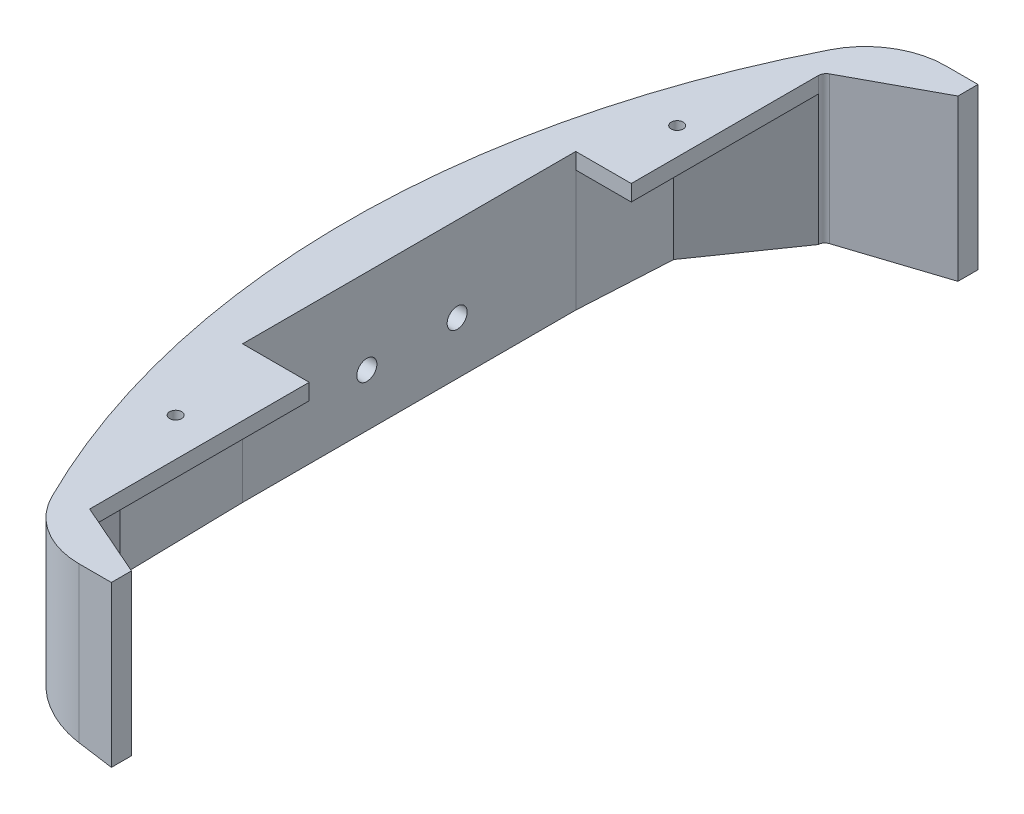
SolidWorks part; units mm, degrees
ref_plane "Front Plane" through (0, 0, 0) normal (0, 0, 1) x (1, 0, 0)
ref_plane "Top Plane" through (0, 0, 0) normal (0, 1, 0) x (1, 0, 0)
ref_plane "Right Plane" through (0, 0, 0) normal (1, 0, 0) x (0, 0, -1)
sketch "front_sketch" plane through (0, 0, 0) normal (0, 1, 0) x (1, 0, 0)
  line L4 (-94.9614, 124.4785) -> (-121.3453, 110.2345)
  line L10 (-122.6787, 107.9994) -> (-122.6787, 48.8108)
  line L24 (-94.9614, 130.8285) -> (-94.9614, 124.4785) construction
  line L25 (-94.9614, 124.4785) -> (-69.5614, 124.4785) construction
  line L28 (-95.6016, -142.8102) -> (-95.6016, -136.4602)
  line L29 (-95.6016, -136.4602) -> (-70.2016, -136.4602) construction
  line L34 (-122.6787, 48.8108) -> (-140.2508, 48.8108)
  line L36 (-140.2508, 48.8108) -> (-140.2508, -56.6452)
  line L43 (-140.2508, -56.6452) -> (-119.167, -56.6452)
  line L44 (-119.167, -56.6452) -> (-119.167, -126.1123)
  line L50 (-119.167, -126.1123) -> (-95.6016, -136.4602)
  line L129 (-94.9614, 130.8285) -> (-69.5614, 130.8285) construction
  line L130 (-94.9614, 130.8285) -> (-69.5614, 130.8285) construction
  line L225 (-95.5505, 130.8285) -> (-157.7358, 130.8285) construction
  line L248 (-94.9614, 130.8285) -> (-95.5505, 130.8285) construction
  line L254 (-94.9614, 130.8285) -> (-95.5505, 130.8285) construction
  line L257 (-94.9614, 130.8285) -> (-105.2412, 130.8285)
  line L258 (-95.5505, 130.8285) -> (-94.9614, 130.8285) construction
  line L259 (-95.6016, -142.8102) -> (-105.7982, -142.8102)
  line L260 (-94.9614, 124.4785) -> (-94.9614, 130.8285)
  line L261 (-94.9614, 130.8285) -> (-95.5505, 130.8285) construction
  line L263 (-95.6016, -142.8102) -> (-70.2016, -142.8102) construction
  line L264 (-95.6016, -142.8102) -> (-70.2016, -142.8102) construction
  line L267 (-97.1554, -142.8102) -> (-95.6016, -142.8102) construction
  line L294 (-94.9614, 130.8285) -> (-95.5505, 130.8285) construction
  line L295 (-157.7358, 130.8285) -> (-157.7358, -142.8102) construction
  line L296 (-157.7358, -142.8102) -> (-97.1554, -142.8102) construction
  line L297 (-95.5505, 130.8285) -> (-157.7358, 130.8285) construction
  arc A41 (-127.9188, 116.8691) -> (-128.5327, -128.7374) centre (116.7138, -6.5464) ccw
  arc A42 (-127.9188, 116.8691) -> (-105.2412, 130.8285) centre (-105.2412, 105.4285) cw
  arc A43 (-128.5327, -128.7374) -> (-105.7982, -142.8102) centre (-105.7982, -117.4102) ccw
  circle A44 centre (-131.2964, 71.9636) radius 1.905
  circle A45 centre (-131.2964, -86.7864) radius 1.905
  arc A48 (-122.6787, 107.9994) -> (-121.3453, 110.2345) centre (-120.1387, 107.9994) cw
  dimension "D12" = 25.4
  dimension "D14" = 25.4
  dimension "D30" = 3.81
  dimension "D4" = 2.54
  dimension "D19" = 6.35
  dimension "D27" = 10.2799
  dimension "D28" = 10.1966
extrude "Boss-Extrude1" add sketch "front_sketch" along normal blind 50.8
sketch "Sketch1" plane through (0, 50.8, 0) normal (0, 1, 0) x (1, 0, 0)
  line L0 (-122.6787, 48.8108) -> (-122.6787, 107.9994)
  line L1 (-122.6787, 107.9994) -> (-138.8333, 78.4051)
  line L2 (-138.8333, 78.4051) -> (-140.2508, 48.8108)
  line L3 (-140.2508, 48.8108) -> (-122.6787, 48.8108)
  line L4 (-119.167, -56.6452) -> (-140.2508, -56.6452)
  line L5 (-119.167, -56.6452) -> (-140.2508, -56.6452) construction
  line L6 (-140.2508, -56.6452) -> (-140.2508, 48.8108) construction
  line L7 (-140.2508, -56.6452) -> (-139.5421, -96.1925)
  line L8 (-139.5421, -96.1925) -> (-119.167, -126.1123)
  line L9 (-119.167, -126.1123) -> (-119.167, -56.6452) construction
  line L10 (-95.6016, -136.4602) -> (-119.167, -126.1123) construction
  line L11 (-119.167, -126.1123) -> (-119.167, -56.6452)
extrude "Cut-Extrude1" cut sketch "Sketch1" along normal blind 48.26 from offset 53.34 offset against normal yes
sketch "Sketch2" plane through (0, 0, 142.8102) normal (0, 0, 1) x (1, 0, 0)
  line L0 (-94.9614, 0) -> (-157.2871, 0)
  line L1 (-157.2871, 0) -> (-157.2871, 10.0565)
  line L2 (-157.2871, 50.8) -> (-157.2871, 0) construction
  line L3 (-157.2871, 10.0565) -> (-94.9614, 0)
extrude "Cut-Extrude2" cut sketch "Sketch2" against normal through all
sketch "Sketch3" plane through (-140.2508, 0, 0) normal (1, 0, 0) x (0, 0, -1)
  circle A0 centre (-17.3122, 23.9848) radius 3.175
  circle A1 centre (11.2741, 23.9848) radius 3.175
extrude "Cut-Extrude3" cut sketch "Sketch3" against normal through all
